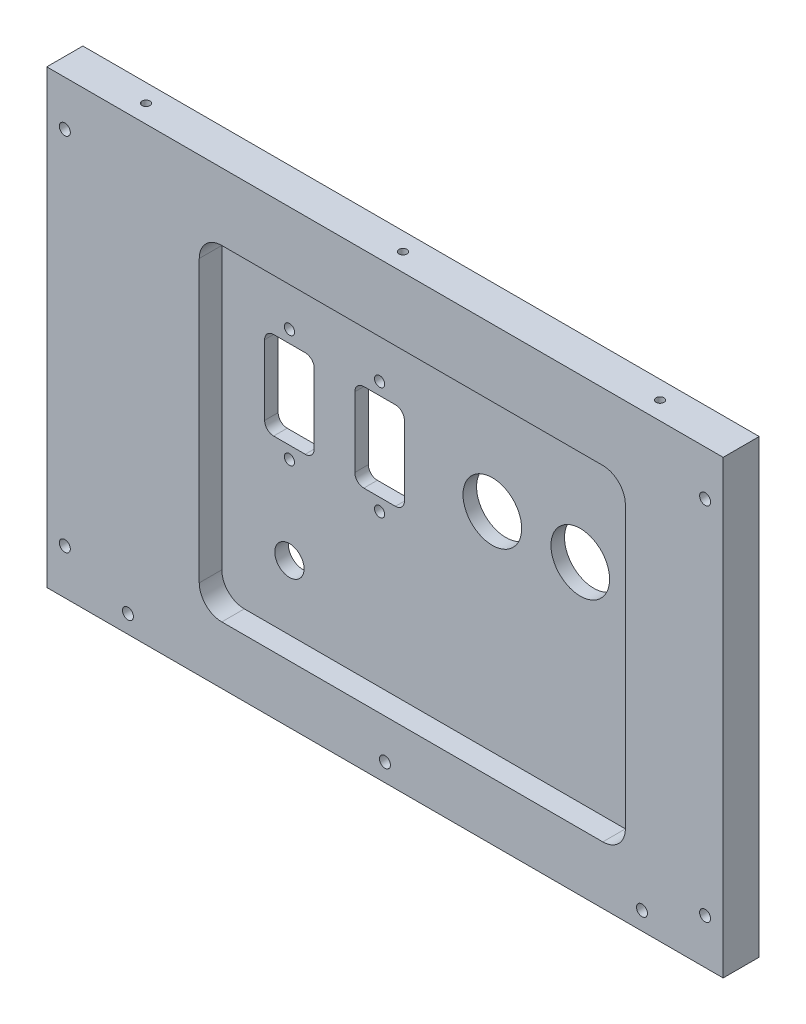
SolidWorks part; units mm, degrees
ref_plane "Front Plane" through (0, 0, 0) normal (0, 0, 1) x (1, 0, 0)
ref_plane "Top Plane" through (0, 0, 0) normal (0, 1, 0) x (1, 0, 0)
ref_plane "Right Plane" through (0, 0, 0) normal (1, 0, 0) x (0, 0, -1)
sketch "Sketch1" plane through (0, 0, 0) normal (0, 0, 1) x (1, 0, 0)
  line L1 (0, 0) -> (150, 0)
  line L2 (0, 0) -> (0, 100)
  line L3 (0, 100) -> (150, 100)
  line L4 (150, 0) -> (150, 100)
  dimension "D1" = 100
  dimension "D2" = 150
extrude "Boss-Extrude1" add sketch "Sketch1" along normal blind 8
hole_wizard "CBORE for #2 Socket Head Cap Screw1" positions "Sketch3" profile "Sketch2" counterbore size "#2" standard "ANSI Inch" end condition through all
sketch "Sketch3" plane through (0, 0, 0) normal (0, 0, -1) x (-1, 0, 0)
  line L0 (-150, 100) -> (0, 100) construction
  line L1 (-142, 100) -> (-142, 0)
  line L2 (0, 0) -> (-150, 0) construction
  line L4 (-150, 0) -> (-150, 100) construction
  line L5 (-8, 100) -> (-8, 0)
  line L7 (0, 100) -> (0, 0) construction
  point P0 (-132, 4)
  point P1 (-18, 4)
  point P3 (-4, 90)
  point P5 (-146, 90)
  point P23 (-4, 90)
  point P32 (-146, 10)
  point P34 (-4, 10)
  point P41 (-75, 4)
  point P42 (-75, 0)
  dimension "D1" = 8
  dimension "D2" = 8
  dimension "D3" = 10
  dimension "D4" = 4
  dimension "D5" = 10
  dimension "D6" = 4
  dimension "D7" = 4
  dimension "D8" = 10
  dimension "D9" = 4
  dimension "D10" = 10
  dimension "D11" = 4
  dimension "D12" = 10
  dimension "D13" = 10
  dimension "D14" = 4
  dimension "D15" = 4
  dimension "D16" = 0
sketch "Sketch2" plane through (132, 4, 0) normal (1, 0, 0) x (0, 1, 0)
  line L0 (0, 0) -> (0, 8)
  line L1 (0, 8) -> (1.2192, 8)
  line L3 (1.2192, 8) -> (1.2192, 2.1844)
  line L4 (1.2192, 2.1844) -> (2.3812, 2.1844)
  line L5 (2.3812, 2.1844) -> (2.3812, 0)
  line L7 (2.3812, 0) -> (0, 0)
  line L11 (0, -6.35) -> (0, 107.95) construction
  dimension "Thru Hole Dia." = 2.4384
  dimension "Thru Hole Depth" = 8
  dimension "C'Bore Dia." = 4.7625
  dimension "C'Bore Depth" = 2.1844
hole_wizard "#2-56 Tapped Hole1" positions "Sketch4" profile "Sketch6" tap size "#2-56" standard "ANSI Inch"
sketch "Sketch4" plane through (0, 100, 0) normal (0, 1, 0) x (1, 0, 0)
  line L0 (8, -8) -> (8, 0)
  line L1 (0, -8) -> (150, -8) construction
  line L2 (0, 0) -> (150, 0) construction
  line L4 (0, -8) -> (0, 0) construction
  line L5 (142, -8) -> (142, 0)
  line L7 (150, -8) -> (150, 0) construction
  point P0 (18, -4)
  point P2 (75, -4)
  point P4 (132, -4)
  point P22 (75, -8)
  dimension "D1" = 8
  dimension "D2" = 10
  dimension "D3" = 8
  dimension "D4" = 10
  dimension "D5" = 0
  dimension "D6" = 4
sketch "Sketch6" plane through (18, 100, 4) normal (1, 0, 0) x (0, 0, 1)
  line L0 (0, 0) -> (0, 20.5342)
  line L1 (0, 20.5342) -> (0.889, 20)
  line L2 (0.889, 20) -> (0.889, 0)
  line L5 (0.889, 0) -> (0, 0)
  line L10 (0, 20.5342) -> (-0.889, 20) construction
  line L11 (0, -6.35) -> (0, 107.95) construction
  dimension "Tap Drill Dia." = 1.778
  dimension "Tap Drill Depth" = 20
  dimension "Drill Angle" = 118
cosmetic thread "Hole Thread1" parameters "D1"=15, "D2"=2.1844
cosmetic thread "Hole Thread2" parameters "D1"=15, "D2"=2.1844
cosmetic thread "Hole Thread3" parameters "D1"=15, "D2"=2.1844
sketch "Sketch7" plane through (0, 0, 8) normal (0, 0, 1) x (1, 0, 0)
  line L0 (45.3138, 68.75) -> (52.3138, 68.75)
  line L1 (43.3138, 66.75) -> (43.3138, 51.25)
  line L2 (45.3138, 49.25) -> (52.3138, 49.25)
  line L3 (54.3138, 66.75) -> (54.3138, 51.25)
  line L4 (65.3138, 68.75) -> (72.3138, 68.75)
  line L5 (63.3138, 66.75) -> (63.3138, 51.25)
  line L6 (65.3138, 49.25) -> (72.3138, 49.25)
  line L7 (74.3138, 66.75) -> (74.3138, 51.25)
  line L9 (0, 0) -> (150, 0) construction
  line L11 (38.8138, 85.1) -> (123.3138, 85.1)
  line L12 (33.8138, 80.1) -> (33.8138, 17.8)
  line L13 (38.8138, 12.8) -> (123.3138, 12.8)
  line L14 (128.3138, 80.1) -> (128.3138, 17.8)
  circle A0 centre (93.8138, 59) radius 6.5
  circle A1 centre (113.3138, 59) radius 6.5
  arc A2 (63.3138, 51.25) -> (65.3138, 49.25) centre (65.3138, 51.25) ccw
  arc A3 (72.3138, 49.25) -> (74.3138, 51.25) centre (72.3138, 51.25) ccw
  arc A4 (72.3138, 68.75) -> (74.3138, 66.75) centre (72.3138, 66.75) cw
  arc A5 (65.3138, 68.75) -> (63.3138, 66.75) centre (65.3138, 66.75) ccw
  arc A6 (52.3138, 68.75) -> (54.3138, 66.75) centre (52.3138, 66.75) cw
  arc A7 (52.3138, 49.25) -> (54.3138, 51.25) centre (52.3138, 51.25) ccw
  arc A8 (43.3138, 51.25) -> (45.3138, 49.25) centre (45.3138, 51.25) ccw
  arc A9 (45.3138, 68.75) -> (43.3138, 66.75) centre (45.3138, 66.75) ccw
  circle A10 centre (48.8138, 27.1) radius 3.25
  arc A11 (38.8138, 85.1) -> (33.8138, 80.1) centre (38.8138, 80.1) ccw
  arc A12 (33.8138, 17.8) -> (38.8138, 12.8) centre (38.8138, 17.8) ccw
  arc A13 (123.3138, 12.8) -> (128.3138, 17.8) centre (123.3138, 17.8) ccw
  arc A14 (123.3138, 85.1) -> (128.3138, 80.1) centre (123.3138, 80.1) cw
  point P4 (74.3138, 59)
  point P5 (54.3138, 59)
  point P10 (43.3138, 59)
  point P16 (48.8138, 46.5)
  point P17 (68.8138, 71.5)
  point P18 (68.8138, 46.5)
  point P20 (63.3138, 59)
  point P21 (48.8138, 49.25)
  point P24 (63.3138, 49.25)
  point P27 (74.3138, 49.25)
  point P30 (74.3138, 68.75)
  point P35 (54.3138, 68.75)
  point P38 (54.3138, 49.25)
  point P43 (43.3138, 68.75)
  point P44 (48.8138, 71.5)
  point P49 (0, 0)
  point P52 (0, 0)
  dimension "D10" = 2
  dimension "D16" = 6.5
  dimension "D21" = 5
  dimension "D1" = 19.5
  dimension "D2" = 11
  dimension "D3" = 19.5
  dimension "D4" = 11
  dimension "D5" = 19.5
  dimension "D6" = 19.5
  dimension "D7" = 0
  dimension "D8" = 59
  dimension "D9" = 0
  dimension "D11" = 2.75
  dimension "D12" = 2.75
  dimension "D13" = 2.75
  dimension "D14" = 2.75
  dimension "D15" = 25.4
  dimension "D17" = 15
  dimension "D18" = 9.5
  dimension "D19" = 16.35
  dimension "D20" = 14.3
extrude "BNC & piezo & BNC thru holes" cut sketch "Sketch7" against normal through all contours L0 A9 L1 A8 L2 A7 L3 A6 | L4 A5 L5 A2 L6 A3 L7 A4 | A0 | A1 | A10 region at (48.8138, 59, 8) region at (68.8138, 59, 8) region at (93.8138, 59, 8) region at (113.3138, 59, 8) region at (48.8138, 27.1, 8)
hole_wizard "#4-40 Tapped Hole1" positions "Sketch12" profile "Sketch13" tap size "#4-40" standard "ANSI Inch" end condition through all
sketch "Sketch12" plane through (0, 0, 8) normal (0, 0, 1) x (1, 0, 0)
  point P0 (48.8138, 71.5)
  point P3 (68.8138, 71.5)
  point P6 (68.8138, 46.5)
  point P9 (48.8138, 46.5)
sketch "Sketch13" plane through (48.8138, 71.5, 8) normal (1, 0, 0) x (0, -1, 0)
  line L0 (0, 0) -> (0, 8)
  line L1 (0, 8) -> (1.1303, 8)
  line L2 (1.1303, 8) -> (1.1303, 0.9271)
  line L3 (1.1303, 0.9271) -> (2.0574, 0)
  line L5 (2.0574, 0) -> (0, 0)
  line L6 (-1.1303, 0.9271) -> (-2.0574, 0) construction
  line L11 (0, -6.35) -> (0, 107.95) construction
  dimension "Thru Tap Drill Dia." = 2.2606
  dimension "Thru Tap Drill Depth" = 8
  dimension "Near C'Sink Dia." = 4.1148
  dimension "Near C'Sink Angle" = 90
cosmetic thread "Hole Thread4" parameters "D2"=2.8448
cosmetic thread "Hole Thread5" parameters "D2"=2.8448
cosmetic thread "Hole Thread6" parameters "D2"=2.8448
cosmetic thread "Hole Thread7" parameters "D2"=2.8448
extrude "Cut-Extrude2" cut sketch "Sketch7<3>" against normal offset from surface (5 mm away) 3 up to face at (49.9441, 71.5, 0)
sketch "Sketch7<3>" plane through (0, 0, 8) normal (0, 0, 1) x (1, 0, 0) same geometry as "Sketch7"
